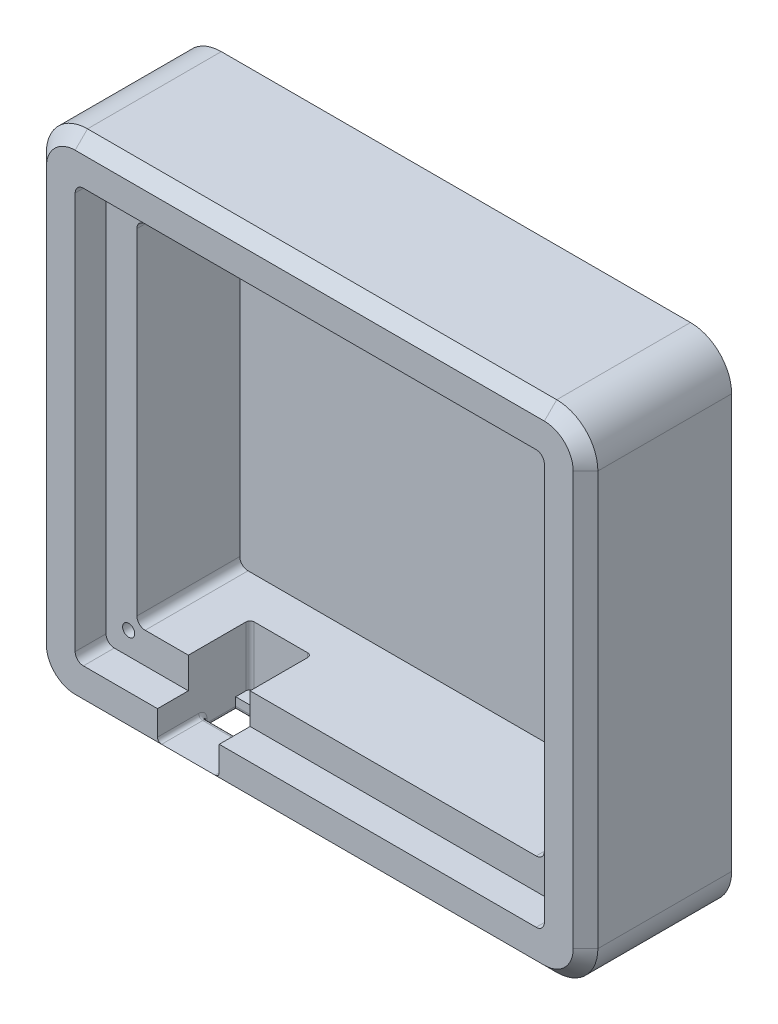
SolidWorks part; units mm, degrees
note: The reader was unsure of these and kept them because the rebuilt part matched: shared geometry of "Base<3>", "Base<4>".
ref_plane "Front Plane" through (0, 0, 0) normal (0, 0, 1) x (1, 0, 0)
ref_plane "Top Plane" through (0, 0, 0) normal (0, 1, 0) x (1, 0, 0)
ref_plane "Right Plane" through (0, 0, 0) normal (1, 0, 0) x (0, 0, -1)
sketch "Base" plane through (0, 0, 0) normal (0, 0, 1) x (1, 0, 0)
  line L0 (0, 5.1857) -> (0, -4.4354) construction
  line L1 (-8.3412, 0) -> (7.1937, 0) construction
  line L2 (-57, 50.25) -> (-57, -50.25)
  line L3 (-51.5, 44.75) -> (51.5, 44.75) construction
  line L4 (-51.5, 44.75) -> (-51.5, -44.75) construction
  line L5 (-51.5, -44.75) -> (51.5, -44.75) construction
  line L6 (51.5, 44.75) -> (51.5, -44.75) construction
  line L7 (-51.5, 44.75) -> (51.5, -44.75) construction
  line L8 (-51.5, -44.75) -> (51.5, 44.75) construction
  line L9 (-57, -50.25) -> (57, -50.25)
  line L10 (57, 50.25) -> (57, -50.25)
  line L11 (-57, 50.25) -> (57, 50.25)
  line L12 (-49.5, 42.75) -> (-49.5, -42.75)
  line L13 (-49.5, -42.75) -> (49.5, -42.75)
  line L14 (49.5, 42.75) -> (49.5, -42.75)
  line L15 (-49.5, 42.75) -> (49.5, 42.75)
  line L16 (-67, 60.25) -> (-67, -60.25)
  line L17 (-67, -60.25) -> (67, -60.25)
  line L18 (67, 60.25) -> (67, -60.25)
  line L19 (-67, 60.25) -> (67, 60.25)
  circle A0 centre (-51.5, 44.75) radius 1.475
  circle A1 centre (51.5, 44.75) radius 1.475
  circle A2 centre (51.5, -44.75) radius 1.475
  circle A3 centre (-51.5, -44.75) radius 1.475
  point P4 (0, 0)
  dimension "D1" = 2.95
  dimension "D2" = 103
  dimension "D3" = 89.5
  dimension "D4" = 5.5
  dimension "D5" = 2
  dimension "D6" = 10
extrude "Boss-Extrude1" add sketch "Base" along normal blind 3 contours L19 L16 L17 L18 L2 L11 L10 L9 | L11 L2 L9 L10 A3 A2 A1 A0 L12 L15 L14 L13 | A2 | A0 | A3 | A1 | L15 L12 L13 L14
extrude "Boss-Extrude2" add sketch "Base<3>" along normal blind 25 from surface at 3 contours L11 L2 L9 L10 A3 A2 A1 A0 L12 L15 L14 L13 starting at face at (0, 0, 3)
sketch "Base<3>" plane through (0, 0, 0) normal (0, 0, 1) x (1, 0, 0) same geometry as "Base"
extrude "Boss-Extrude3" add sketch "Base<4>" along normal blind 32.5 from surface at 3 contours L19 L16 L17 L18 L2 L11 L10 L9 starting at face at (0, 0, 3)
sketch "Base<4>" plane through (0, 0, 0) normal (0, 0, 1) x (1, 0, 0) same geometry as "Base"
sketch "Sketch2" plane through (0, 0, 35.5) normal (0, 0, 1) x (1, 0, 0)
  line L0 (-57, -50.25) -> (-57, 47.25) construction
  line L2 (-57, -50.25) -> (-57, 50.25) construction
  line L3 (49.5, -42.75) -> (-49.5, -42.75) construction
  line L4 (-37, -42.75) -> (-22, -42.75)
  line L5 (-37, -42.75) -> (-37, -57.25)
  line L6 (-37, -57.25) -> (-22, -57.25)
  line L7 (-22, -42.75) -> (-22, -57.25)
  line L8 (67, -60.25) -> (-67, -60.25) construction
  point P1 (-57, 0)
  dimension "D1" = 3
  dimension "D2" = 15
  dimension "D3" = 20
extrude "Cut-Extrude1" cut sketch "Sketch2" against normal offset from surface (22.5 mm away) 15 up to face at (0, 0, 28)
sketch "Sketch3" plane through (0, -60.25, 0) normal (0, -1, 0) x (1, 0, 0)
  line L1 (-37, 24.5) -> (-22, 24.5)
  line L2 (-37, 24.5) -> (-37, 16.5)
  line L3 (-37, 16.5) -> (-22, 16.5)
  line L4 (-22, 24.5) -> (-22, 16.5)
  line L5 (-37, 13) -> (-37, 35.5) construction
  line L6 (-22, 13) -> (-22, 35.5) construction
  line L7 (-37, 13) -> (-22, 13) construction
  point P4 (-29.5, 13)
  point P8 (-37, 20.5)
  point P11 (-22, 20.5)
  dimension "D1" = 3.5
  dimension "D2" = 8
extrude "Cut-Extrude2" cut sketch "Sketch3" against normal up to surface (3 mm away) contours L4 L3 L2 L1 up to face at (-29.5, -57.25, 24.25)
fillet "Fillet1" radius 10 4 edges at (67, -60.25, 17.75) (67, 60.25, 17.75) (-67, 60.25, 17.75) (-67, -60.25, 17.75)
fillet "Fillet2" radius 2 8 edges at (49.5, 42.75, 15.5) (49.5, -42.75, 15.5) (-49.5, 42.75, 15.5) (-49.5, -42.75, 15.5) (-57, -50.25, 31.75) (-57, 50.25, 31.75) (57, 50.25, 31.75) (57, -50.25, 31.75)
fillet "Fillet3" radius 1 11 edges at (-22, -57.25, 30) (-37, -57.25, 30) (-37, -60.25, 20.5) (-22, -60.25, 20.5) (-29.5, -57.25, 24.5) (-37, -58.75, 24.5) (-29.5, -60.25, 24.5) (-22, -58.75, 24.5) (-37, -50, 13) (-22, -50, 13) (-29.5, -60.25, 16.5)
chamfer "Chamfer1" distance 3 angle 45 8 edges at (67, 0, 35.5) (64.0711, -57.3211, 35.5) (64.0711, 57.3211, 35.5) (0, -60.25, 35.5) (0, 60.25, 35.5) (-64.0711, -57.3211, 35.5) (-64.0711, 57.3211, 35.5) (-67, 0, 35.5)
